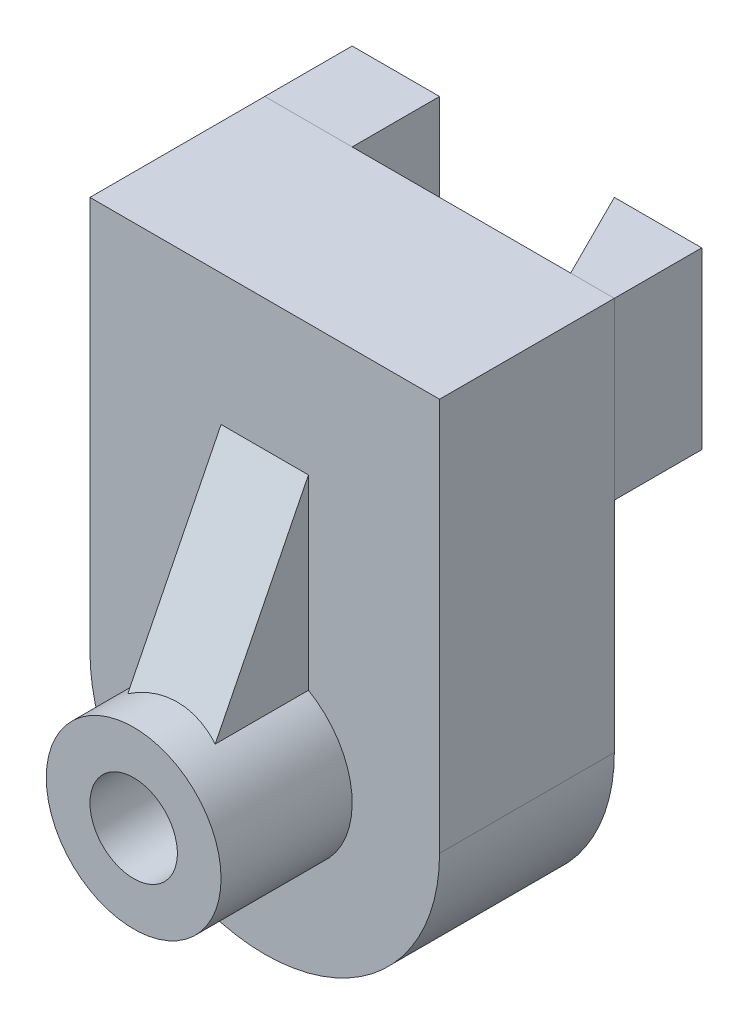
SolidWorks part; units mm, degrees
ref_plane "Front Plane" through (0, 0, 0) normal (1, 0, 0) x (0, 1, 0)
ref_plane "Top Plane" through (0, 0, 0) normal (0, 0, 1) x (0, 1, 0)
ref_plane "Right Plane" through (0, 0, 0) normal (0, 1, 0) x (-1, 0, 0)
sketch "Sketch1" plane through (0, 0, 0) normal (0, 1, 0) x (-1, 0, 0)
  line L0 (0, -42.1759) -> (0, 42.1759) construction
  line L5 (20, 0) -> (-20, 0)
  line L6 (-20, 0) -> (-20, 20)
  line L7 (-20, 20) -> (20, 20)
  line L8 (20, 20) -> (20, 0)
  line L9 (-20, 0) -> (-20, -10)
  line L10 (-20, -10) -> (-10, -10)
  line L11 (-10, -10) -> (-15, 0)
  line L12 (20, 0) -> (20, -10)
  line L13 (20, -10) -> (10, -10)
  line L14 (10, -10) -> (10, 0)
  point P8 (0, 0)
  dimension "D1" = 10
  dimension "D2" = 10
  dimension "D3" = 5
  dimension "D4" = 40
  dimension "D5" = 20
extrude "Boss-Extrude1" add sketch "Sketch1" against normal blind 65 contours L0 L5 L8 L7 | L5 L0 L7 L6 region at (10, 0, 10) region at (-10, 0, 10)
extrude "Boss-Extrude2" add sketch "Sketch1<4>" against normal blind 20 separate body contours L10 L11 L5 L9 | L14 L13 L12 L5 region at (-15, 0, -5) region at (16.1111, 0, -5.5556)
sketch "Sketch1<4>" plane through (0, 0, 0) normal (0, 1, 0) x (-1, 0, 0) same geometry as "Sketch1"
fillet "Fillet1" radius 20 2 edges at (-20, -65, 10) (20, -65, 10)
sketch "Sketch3" plane through (0, 0, 20) normal (0, 0, 1) x (1, 0, 0)
  line L0 (0, 0) -> (0, -81.0987) construction
  line L1 (-20, -45) -> (20, -45) construction
  circle A0 centre (0, -45) radius 10
  dimension "D1" = 20
extrude "Boss-Extrude3" add sketch "Sketch3" along normal blind 15
sketch "Sketch5" plane through (0, 0, 0) normal (1, 0, 0) x (0, 1, 0)
  line L0 (-35, 30) -> (-15, 20)
  line L1 (-35, 20) -> (-35, 35) construction
  line L2 (-45, 20) -> (0, 20) construction
  dimension "D1" = 20
  dimension "D2" = 5
rib "Rib3" sketch "Sketch5" sketch "Sketch5" thickness 10 extrusion direction parallel to sketch draft on no parameters "D1"=10
hole_wizard "Ø10.0 (10) Diameter Hole1" positions "3DSketch1" profile "Sketch8" hole size "Ø10.0" standard "ISO" end condition through all
sketch3d "3DSketch1"
  line L0 (0, -45, 20) -> (0, -45, 0) construction
  point P0 (0, -45, 0)
sketch "Sketch8" plane through (0, -45, 0) normal (1, 0, 0) x (0, 1, 0)
  line L0 (0, 0) -> (0, 35)
  line L1 (0, 35) -> (5, 35)
  line L2 (5, 35) -> (5, 5)
  line L3 (5, 5) -> (10, 0)
  line L5 (10, 0) -> (0, 0)
  line L6 (-5, 5) -> (-10, 0) construction
  line L11 (0, -6.35) -> (0, 107.95) construction
  dimension "Thru Hole Dia." = 10
  dimension "Thru Hole Depth" = 35
  dimension "Near C'Sink Dia." = 20
  dimension "Near C'Sink Angle" = 90
